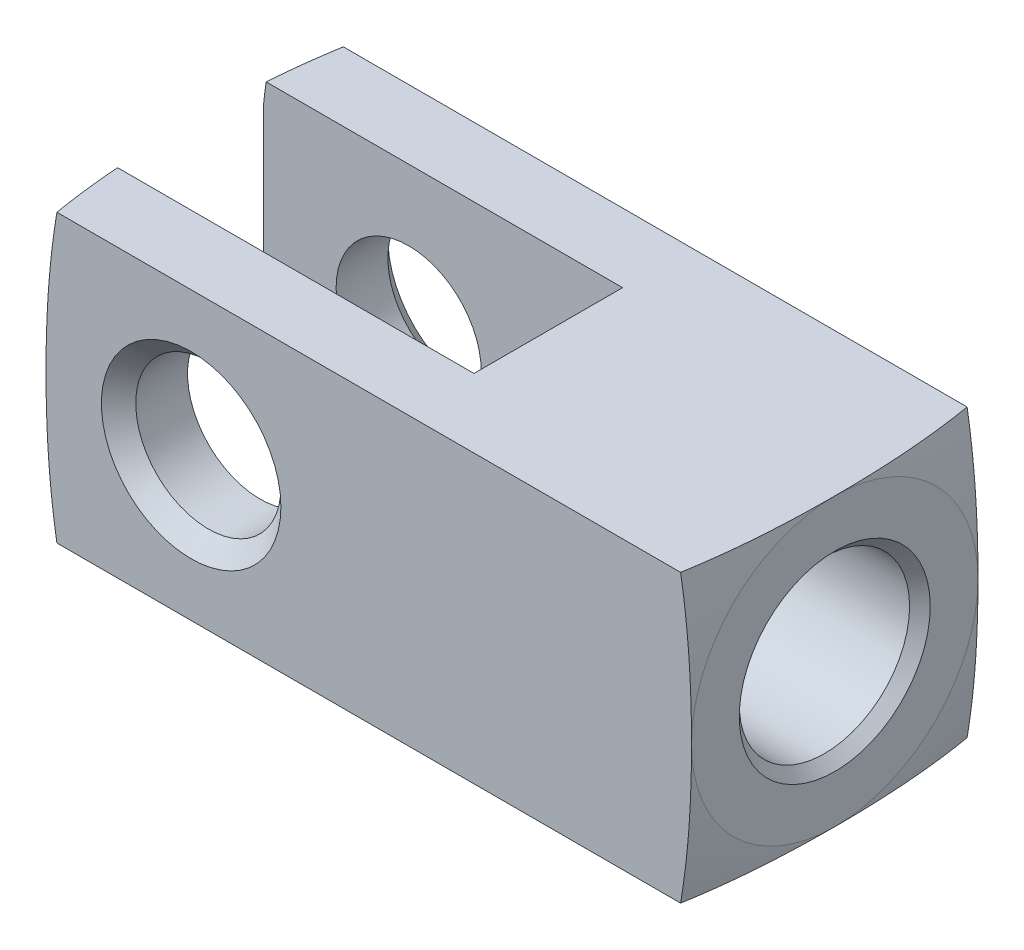
SolidWorks part; units mm, degrees
material "Plain Carbon Steel"
ref_plane "Front Plane" through (0, 0, 0) normal (0, 0, 1) x (1, 0, 0)
ref_plane "Top Plane" through (0, 0, 0) normal (0, 1, 0) x (1, 0, 0)
ref_plane "Right Plane" through (0, 0, 0) normal (1, 0, 0) x (0, 0, -1)
sketch "Sketch1" plane through (0, 0, 0) normal (0, 0, 1) x (1, 0, 0)
  line L0 (-9.652, 9.525) -> (-9.652, -9.525)
  line L1 (-9.652, -9.525) -> (33.274, -9.525)
  line L2 (33.274, -9.525) -> (33.274, 9.525)
  line L3 (33.274, 9.525) -> (-9.652, 9.525)
extrude "Boss-Extrude1" add sketch "Sketch1" against normal blind 9.525 and the other way blind 9.525
sketch "Sketch2" plane through (0, 0, 0) normal (0, 1, 0) x (1, 0, 0)
  line L0 (-9.652, 4.9403) -> (-9.652, -4.9403)
  line L1 (-9.652, -4.9403) -> (14.224, -4.9403)
  line L2 (14.224, -4.9403) -> (14.224, 4.9403)
  line L3 (14.224, 4.9403) -> (-9.652, 4.9403)
extrude "Cut-Extrude1" cut sketch "Sketch2" along normal blind 9.525 and the other way blind 9.525
hole_wizard "Hole1" positions "Sketch4" profile "Sketch3" legacy
sketch "Sketch4" plane through (33.274, 0, 0) normal (1, 0, 0) x (0, 0, -1)
  point P0 (0, 0)
sketch "Sketch3" plane through (33.274, 0, 0) normal (0, 1, 0) x (0, 0, -1)
  line L0 (0, 0) -> (0, 19.05)
  line L1 (0, 19.05) -> (5.6629, 19.05)
  line L2 (5.6629, 19.05) -> (5.6629, 0.6871)
  line L3 (5.6629, 0.6871) -> (6.35, 0)
  line L4 (6.35, 0) -> (0, 0)
  line L5 (0, -6.4453) -> (0, 115.525) construction
  line L6 (-5.6629, 0.6871) -> (-6.35, 0) construction
  dimension "Diameter" = 11.3259
  dimension "Depth" = 19.05
  dimension "C-Sink Angle" = 90
  dimension "C-Sink Diameter" = 12.7
cosmetic thread "Cosmetic Thread1" parameters "D1"=19.05, "D2"=12.7
ref_plane "Plane1" through (0, 0, 6.35) normal (0, 0, 1) x (1, 0, 0)
ref_plane "Plane2" through (0, 0, -6.35) normal (0, 0, 1) x (1, 0, 0)
ref_plane "Plane3" through (23.876, 0, 0) normal (1, 0, 0) x (0, 0, -1)
sketch "Sketch5" plane through (0, 0, 0) normal (1, 0, 0) x (0, 0, -1)
  line L0 (-9.525, 0) -> (-9.525, 5.969)
  line L1 (-9.525, 5.969) -> (-8.382, 4.826)
  line L2 (-8.382, 4.826) -> (8.382, 4.826)
  line L3 (8.382, 4.826) -> (9.525, 5.969)
  line L4 (9.525, 5.969) -> (9.525, 0)
  line L5 (9.525, 0) -> (-9.525, 0)
  line L6 (9.525, 0) -> (-9.525, 0) construction
revolve "Cut-Revolve1" cut sketch "Sketch5" angle 360 about L6 reverse direction yes
sketch "Sketch6" plane through (0, 0, 0) normal (0, 0, 1) x (1, 0, 0)
  line L0 (33.274, 0) -> (33.274, 9.525)
  line L1 (30.734, 19.05) -> (42.799, 19.05)
  line L2 (42.799, 19.05) -> (42.799, 0)
  line L3 (42.799, 0) -> (33.274, 0)
  line L4 (42.799, 0) -> (33.274, 0) construction
  arc A0 (33.274, 9.525) -> (30.734, 19.05) centre (-3.7148, 4.7625) ccw
revolve "Cut-Revolve2" cut sketch "Sketch6" angle 360 about L4 reverse direction yes
sketch "Sketch7" plane through (0, 0, 0) normal (0, 0, 1) x (1, 0, 0)
  line L0 (-19.177, 0) -> (-19.177, 19.05)
  line L1 (-19.177, 19.05) -> (-7.112, 19.05)
  line L2 (-9.652, 9.525) -> (-9.652, 0)
  line L3 (-9.652, 0) -> (-19.177, 0)
  line L4 (-9.652, 0) -> (-19.177, 0) construction
  arc A0 (-7.112, 19.05) -> (-9.652, 9.525) centre (27.3367, 4.7625) ccw
revolve "Cut-Revolve3" cut sketch "Sketch7" angle 360 about L4 reverse direction yes
ref_plane "Plane4" through (33.274, 0, 0) normal (1, 0, 0) x (0, 0, -1)
ref_plane "Plane5" through (14.224, 0, 0) normal (1, 0, 0) x (0, 0, -1)
ref_plane "dummy XY" through (0, 0, 0) normal (0, 0, 1) x (1, 0, 0)
ref_plane "dummy XZ" through (0, 0, 0) normal (0, -1, 0) x (-1, 0, 0)
ref_plane "dummy YZ" through (0, 0, 0) normal (1, 0, 0) x (0, 0, -1)
ref_axis "dummy X" through (-80.9, 0, 0) along (1, 0, 0)
ref_axis "dummy Y" through (0, -50, 0) along (0, 1, 0)
ref_axis "dummy Z" through (0, 0, 80.9) along (0, 0, -1)
sketch3d "dummy"
  point P0 (0, 0, 0)
ref_plane "h1 XY" through (0, 0, 0) normal (0, 0, 1) x (1, 0, 0)
ref_plane "h1 XZ" through (0, 9.525, 0) normal (0, -1, 0) x (-1, 0, 0)
ref_plane "h1 YZ" through (-9.652, 0, 0) normal (1, 0, 0) x (0, 0, -1)
ref_axis "h1 X" through (-80.9, 9.525, 0) along (1, 0, 0)
ref_axis "h1 Y" through (-9.652, -50, 0) along (0, 1, 0)
ref_axis "h1 Z" through (-9.652, 9.525, 80.9) along (0, 0, -1)
sketch3d "h1"
  point P0 (-9.652, 9.525, 0)
ref_plane "h2 XY" through (0, 0, 0) normal (0, 0, 1) x (1, 0, 0)
ref_plane "h2 XZ" through (0, -9.525, 0) normal (0, -1, 0) x (-1, 0, 0)
ref_plane "h2 YZ" through (-9.652, 0, 0) normal (1, 0, 0) x (0, 0, -1)
ref_axis "h2 X" through (-80.9, -9.525, 0) along (1, 0, 0)
ref_axis "h2 Y" through (-9.652, -50, 0) along (0, 1, 0)
ref_axis "h2 Z" through (-9.652, -9.525, 80.9) along (0, 0, -1)
sketch3d "h2"
  point P0 (-9.652, -9.525, 0)
ref_plane "l1 XY" through (0, 0, 0) normal (0, 0, 1) x (1, 0, 0)
ref_plane "l1 XZ" through (0, 9.525, 0) normal (0, -1, 0) x (-1, 0, 0)
ref_plane "l1 YZ" through (33.274, 0, 0) normal (1, 0, 0) x (0, 0, -1)
ref_axis "l1 X" through (-80.9, 9.525, 0) along (1, 0, 0)
ref_axis "l1 Y" through (33.274, -50, 0) along (0, 1, 0)
ref_axis "l1 Z" through (33.274, 9.525, 80.9) along (0, 0, -1)
sketch3d "l1"
  point P0 (33.274, 9.525, 0)
ref_plane "l11 XY" through (0, 0, 0) normal (0, 0, 1) x (1, 0, 0)
ref_plane "l11 XZ" through (0, 9.525, 0) normal (0, -1, 0) x (-1, 0, 0)
ref_plane "l11 YZ" through (33.274, 0, 0) normal (1, 0, 0) x (0, 0, -1)
ref_axis "l11 X" through (-80.9, 9.525, 0) along (1, 0, 0)
ref_axis "l11 Y" through (33.274, -50, 0) along (0, 1, 0)
ref_axis "l11 Z" through (33.274, 9.525, 80.9) along (0, 0, -1)
sketch3d "l11"
  point P0 (33.274, 9.525, 0)
ref_plane "l12 XY" through (0, 0, 0) normal (0, 0, 1) x (1, 0, 0)
ref_plane "l12 XZ" through (0, 9.525, 0) normal (0, -1, 0) x (-1, 0, 0)
ref_plane "l12 YZ" through (0, 0, 0) normal (1, 0, 0) x (0, 0, -1)
ref_axis "l12 X" through (-80.9, 9.525, 0) along (1, 0, 0)
ref_axis "l12 Y" through (0, -50, 0) along (0, 1, 0)
ref_axis "l12 Z" through (0, 9.525, 80.9) along (0, 0, -1)
sketch3d "l12"
  point P0 (0, 9.525, 0)
ref_plane "l2 XY" through (0, 0, 0) normal (0, 0, 1) x (1, 0, 0)
ref_plane "l2 XZ" through (0, 9.525, 0) normal (0, -1, 0) x (-1, 0, 0)
ref_plane "l2 YZ" through (-9.652, 0, 0) normal (1, 0, 0) x (0, 0, -1)
ref_axis "l2 X" through (-80.9, 9.525, 0) along (1, 0, 0)
ref_axis "l2 Y" through (-9.652, -50, 0) along (0, 1, 0)
ref_axis "l2 Z" through (-9.652, 9.525, 80.9) along (0, 0, -1)
sketch3d "l2"
  point P0 (-9.652, 9.525, 0)
ref_plane "l21 XY" through (0, 0, 0) normal (0, 1, 0) x (1, 0, 0)
ref_plane "l21 XZ" through (0, 0, 0) normal (0, 0, 1) x (1, 0, 0)
ref_plane "l21 YZ" through (33.274, 0, 0) normal (1, 0, 0) x (0, 0, -1)
ref_axis "l21 X" through (-80.9, 0, 0) along (1, 0, 0)
ref_axis "l21 Y" through (33.274, 0, 50) along (0, 0, -1)
ref_axis "l21 Z" through (33.274, 50, 0) along (0, -1, 0)
sketch3d "l21"
  point P0 (33.274, 0, 0)
ref_plane "l22 XY" through (0, 0, 0) normal (0, 1, 0) x (1, 0, 0)
ref_plane "l22 XZ" through (0, 0, 0) normal (0, 0, 1) x (1, 0, 0)
ref_plane "l22 YZ" through (14.224, 0, 0) normal (1, 0, 0) x (0, 0, -1)
ref_axis "l22 X" through (-80.9, 0, 0) along (1, 0, 0)
ref_axis "l22 Y" through (14.224, 0, 50) along (0, 0, -1)
ref_axis "l22 Z" through (14.224, 50, 0) along (0, -1, 0)
sketch3d "l22"
  point P0 (14.224, 0, 0)
ref_plane "piston_rod_clevis XY" through (33.274, 0, 0) normal (1, 0, 0) x (0, 0, -1)
ref_plane "piston_rod_clevis XZ" through (0, 0, 0) normal (0, -1, 0) x (-1, 0, 0)
ref_plane "piston_rod_clevis YZ" through (0, 0, 0) normal (0, 0, -1) x (-1, 0, 0)
ref_axis "piston_rod_clevis X" through (33.274, 0, 80.9) along (0, 0, -1)
ref_axis "piston_rod_clevis Y" through (33.274, -50, 0) along (0, 1, 0)
ref_axis "piston_rod_clevis Z" through (80.9, 0, 0) along (-1, 0, 0)
sketch3d "piston_rod_clevis"
  point P0 (33.274, 0, 0)
ref_plane "rod_clevis_body XY" through (0, 0, 0) normal (0, 0, 1) x (1, 0, 0)
ref_plane "rod_clevis_body XZ" through (0, 0, 0) normal (0, -1, 0) x (-1, 0, 0)
ref_plane "rod_clevis_body YZ" through (0, 0, 0) normal (1, 0, 0) x (0, 0, -1)
ref_axis "rod_clevis_body X" through (-80.9, 0, 0) along (1, 0, 0)
ref_axis "rod_clevis_body Y" through (0, -50, 0) along (0, 1, 0)
ref_axis "rod_clevis_body Z" through (0, 0, 80.9) along (0, 0, -1)
sketch3d "rod_clevis_body"
  point P0 (0, 0, 0)
ref_plane "th1 XY" through (0, 0, 0) normal (0, 0, 1) x (1, 0, 0)
ref_plane "th1 XZ" through (0, 6.35, 0) normal (0, -1, 0) x (-1, 0, 0)
ref_plane "th1 YZ" through (33.274, 0, 0) normal (1, 0, 0) x (0, 0, -1)
ref_axis "th1 X" through (-80.9, 6.35, 0) along (1, 0, 0)
ref_axis "th1 Y" through (33.274, -50, 0) along (0, 1, 0)
ref_axis "th1 Z" through (33.274, 6.35, 80.9) along (0, 0, -1)
sketch3d "th1"
  point P0 (33.274, 6.35, 0)
ref_plane "th2 XY" through (0, 0, 0) normal (0, 0, 1) x (1, 0, 0)
ref_plane "th2 XZ" through (0, -6.35, 0) normal (0, -1, 0) x (-1, 0, 0)
ref_plane "th2 YZ" through (33.274, 0, 0) normal (1, 0, 0) x (0, 0, -1)
ref_axis "th2 X" through (-80.9, -6.35, 0) along (1, 0, 0)
ref_axis "th2 Y" through (33.274, -50, 0) along (0, 1, 0)
ref_axis "th2 Z" through (33.274, -6.35, 80.9) along (0, 0, -1)
sketch3d "th2"
  point P0 (33.274, -6.35, 0)
ref_plane "to_cylinder XY" through (14.224, 0, 0) normal (1, 0, 0) x (0, 0, -1)
ref_plane "to_cylinder XZ" through (0, 0, 0) normal (0, -1, 0) x (-1, 0, 0)
ref_plane "to_cylinder YZ" through (0, 0, 0) normal (0, 0, -1) x (-1, 0, 0)
ref_axis "to_cylinder X" through (14.224, 0, 80.9) along (0, 0, -1)
ref_axis "to_cylinder Y" through (14.224, -50, 0) along (0, 1, 0)
ref_axis "to_cylinder Z" through (80.9, 0, 0) along (-1, 0, 0)
sketch3d "to_cylinder"
  point P0 (14.224, 0, 0)
ref_plane "w1 XY" through (0, 0, 0) normal (0, 1, 0) x (1, 0, 0)
ref_plane "w1 XZ" through (0, 0, -9.525) normal (0, 0, 1) x (1, 0, 0)
ref_plane "w1 YZ" through (33.274, 0, 0) normal (1, 0, 0) x (0, 0, -1)
ref_axis "w1 X" through (-80.9, 0, -9.525) along (1, 0, 0)
ref_axis "w1 Y" through (33.274, 0, 50) along (0, 0, -1)
ref_axis "w1 Z" through (33.274, 50, -9.525) along (0, -1, 0)
sketch3d "w1"
  point P0 (33.274, 0, -9.525)
ref_plane "w11 XY" through (0, 0, 0) normal (0, 1, 0) x (1, 0, 0)
ref_plane "w11 XZ" through (0, 0, -4.9403) normal (0, 0, 1) x (1, 0, 0)
ref_plane "w11 YZ" through (-9.652, 0, 0) normal (1, 0, 0) x (0, 0, -1)
ref_axis "w11 X" through (-80.9, 0, -4.9403) along (1, 0, 0)
ref_axis "w11 Y" through (-9.652, 0, 50) along (0, 0, -1)
ref_axis "w11 Z" through (-9.652, 50, -4.9403) along (0, -1, 0)
sketch3d "w11"
  point P0 (-9.652, 0, -4.9403)
ref_plane "w12 XY" through (0, 0, 0) normal (0, 1, 0) x (1, 0, 0)
ref_plane "w12 XZ" through (0, 0, 4.9403) normal (0, 0, 1) x (1, 0, 0)
ref_plane "w12 YZ" through (-9.652, 0, 0) normal (1, 0, 0) x (0, 0, -1)
ref_axis "w12 X" through (-80.9, 0, 4.9403) along (1, 0, 0)
ref_axis "w12 Y" through (-9.652, 0, 50) along (0, 0, -1)
ref_axis "w12 Z" through (-9.652, 50, 4.9403) along (0, -1, 0)
sketch3d "w12"
  point P0 (-9.652, 0, 4.9403)
ref_plane "w2 XY" through (0, 0, 0) normal (0, 1, 0) x (1, 0, 0)
ref_plane "w2 XZ" through (0, 0, 9.525) normal (0, 0, 1) x (1, 0, 0)
ref_plane "w2 YZ" through (33.274, 0, 0) normal (1, 0, 0) x (0, 0, -1)
ref_axis "w2 X" through (-80.9, 0, 9.525) along (1, 0, 0)
ref_axis "w2 Y" through (33.274, 0, 50) along (0, 0, -1)
ref_axis "w2 Z" through (33.274, 50, 9.525) along (0, -1, 0)
sketch3d "w2"
  point P0 (33.274, 0, 9.525)
